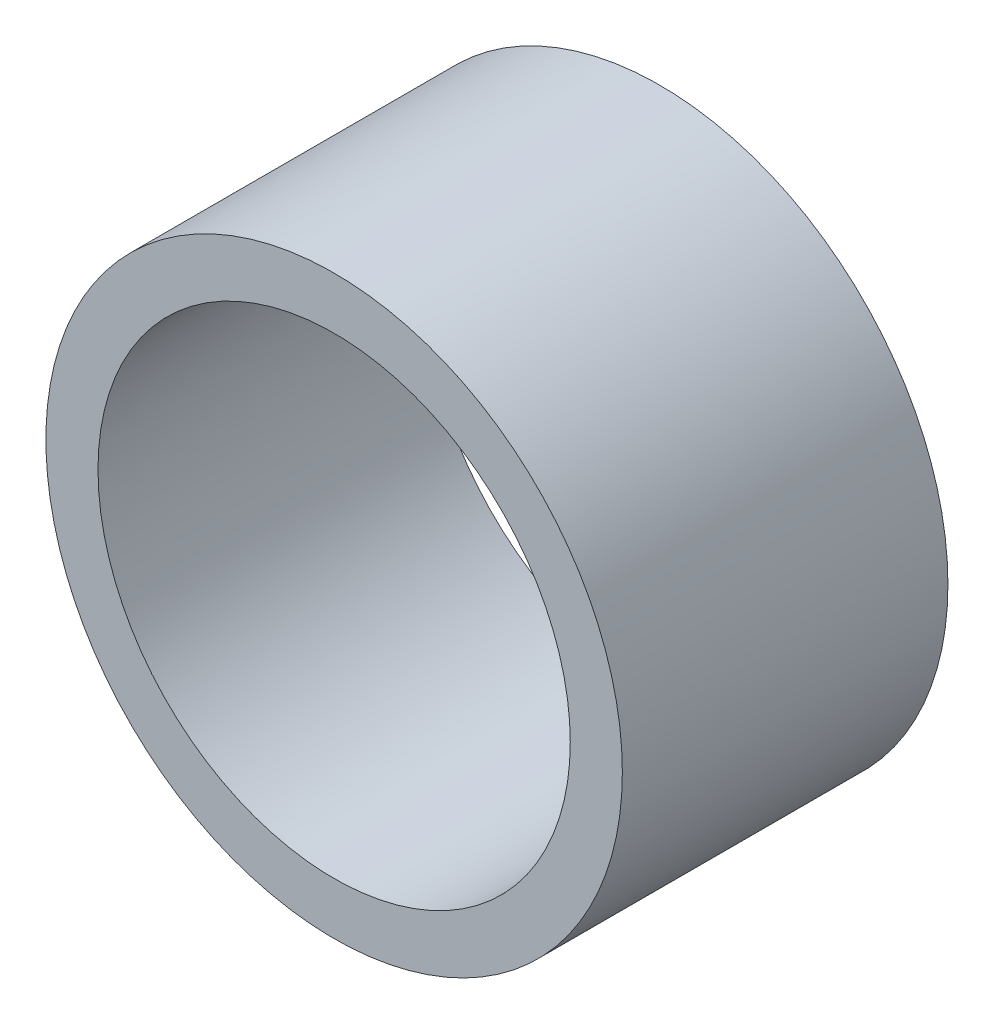
SolidWorks part; units mm, degrees
ref_plane "Front Plane" through (0, 0, 0) normal (0, 0, 1) x (1, 0, 0)
ref_plane "Top Plane" through (0, 0, 0) normal (0, 1, 0) x (1, 0, 0)
ref_plane "Right Plane" through (0, 0, 0) normal (1, 0, 0) x (0, 0, -1)
sketch "Sketch2" plane through (0, 0, 0) normal (0, 0, 1) x (1, 0, 0)
  circle A0 centre (0, 0) radius 17.272
  circle A1 centre (0, 0) radius 21.082
  dimension "D1" = 34.544
  dimension "D2" = 42.164
extrude "Boss-Extrude1" add sketch "Sketch2" along normal blind 23.8125 contours A1 A0 region at (-20.4857, 0, 0)
